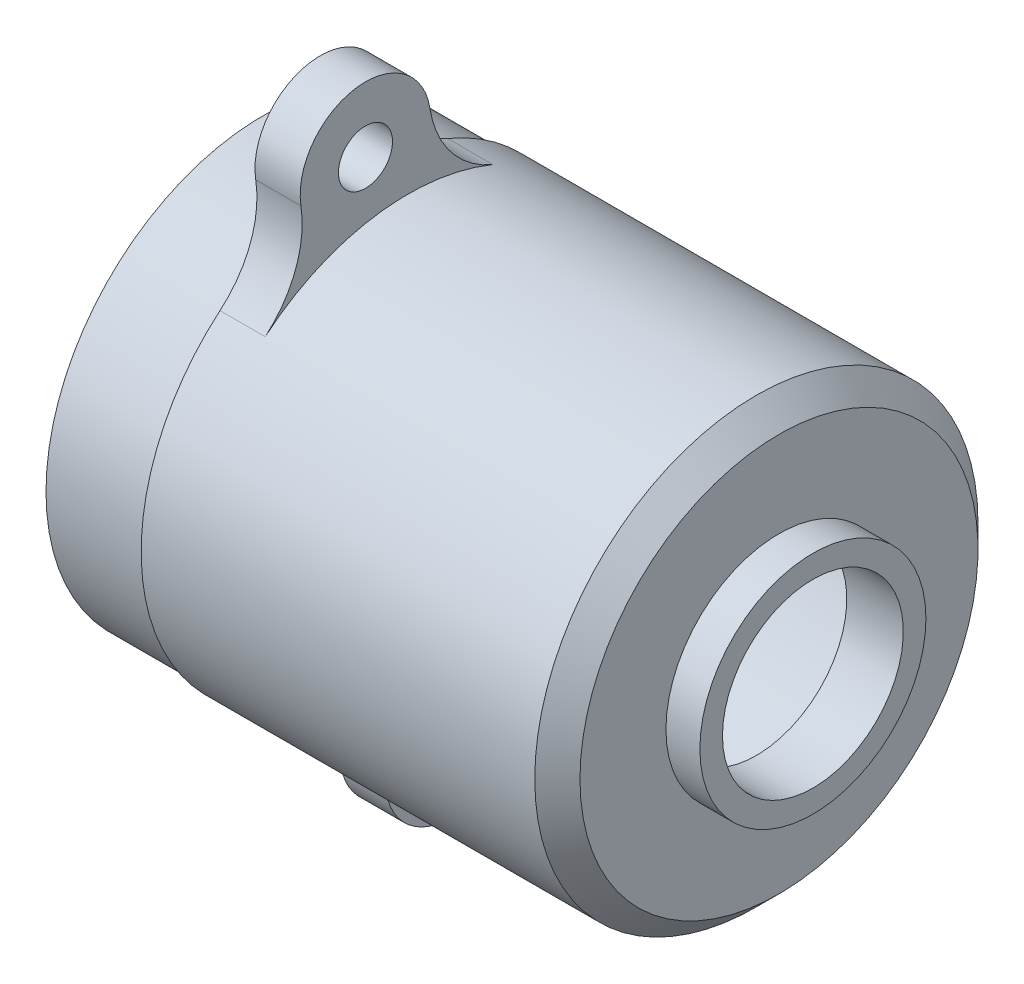
SolidWorks part; units mm, degrees
material "6061-T6 (SS)"
ref_plane "Front Plane" through (0, 0, 0) normal (0, 0, 1) x (1, 0, 0)
ref_plane "Top Plane" through (0, 0, 0) normal (0, 1, 0) x (1, 0, 0)
ref_plane "Right Plane" through (0, 0, 0) normal (1, 0, 0) x (0, 0, -1)
other "Center of Mass"
sketch "Sketch1" plane through (-25.4, 0, 0) normal (1, 0, 0) x (0, 0, -1)
  line L0 (0, 0) -> (-2.9885, 19.3009) construction
  line L1 (-0.1168, 15.7295) -> (1.5403, 20.0021) construction
  line L2 (1.5403, 20.0021) -> (-1.3314, 23.5735) construction
  line L3 (-1.3314, 23.5735) -> (-5.8601, 22.8723) construction
  line L4 (-5.8601, 22.8723) -> (-7.5172, 18.5996) construction
  line L5 (-7.5172, 18.5996) -> (-4.6456, 15.0282) construction
  line L6 (-4.6456, 15.0282) -> (-0.1168, 15.7295) construction
  line L7 (4.6456, -15.0282) -> (0.1168, -15.7295) construction
  line L8 (0.1168, -15.7295) -> (-1.5403, -20.0021) construction
  line L9 (-1.5403, -20.0021) -> (1.3314, -23.5735) construction
  line L10 (1.3314, -23.5735) -> (5.8601, -22.8723) construction
  line L11 (5.8601, -22.8723) -> (7.5172, -18.5996) construction
  line L12 (7.5172, -18.5996) -> (4.6456, -15.0282) construction
  line L13 (-7.5172, 18.5996) -> (1.5403, 20.0021) construction
  line L15 (0, 0) -> (12.0771, 1.87) construction
  circle A0 centre (0, 0) radius 13.9746
  circle A1 centre (0, 0) radius 15.5621 construction
  circle A3 centre (2.9885, -19.3009) radius 3.9688 construction
  circle A4 centre (-2.9885, 19.3009) radius 8.7404 construction
  arc A8 (-10.0273, 11.901) -> (-5.9586, -14.3762) centre (0, 0) ccw
  arc A9 (5.9586, 14.3762) -> (10.0273, -11.901) centre (0, 0) cw
  circle A16 centre (-2.9885, 19.3009) radius 2.667 construction
  circle A17 centre (2.9885, -19.3009) radius 2.667 construction
  arc A18 (-9.6776, 36.4316) -> (-11.5083, 22.6659) centre (127.0686, 11.2409) ccw construction
  arc A19 (4.4842, 36.4316) -> (4.6143, 28.807) centre (76.9988, 33.8561) ccw construction
  arc A20 (-10.0273, 11.901) -> (-7.5172, 18.5996) centre (-14.7303, 17.4828) ccw
  arc A21 (-7.5172, 18.5996) -> (1.5403, 20.0021) centre (-2.9885, 19.3009) cw
  arc A22 (1.5403, 20.0021) -> (5.9586, 14.3762) centre (8.7533, 21.1189) ccw
  arc A23 (7.5172, -18.5996) -> (10.0273, -11.901) centre (14.7303, -17.4828) cw
  arc A24 (-1.5403, -20.0021) -> (7.5172, -18.5996) centre (2.9885, -19.3009) ccw
  arc A25 (-5.9586, -14.3762) -> (-1.5403, -20.0021) centre (-8.7533, -21.1189) cw
  point P4 (-2.3812, 15.3788)
  dimension "D1" = 27.9492
  dimension "D4" = 5.334
  dimension "D2" = 1.5875
  dimension "D3" = 7.9375
extrude "Boss-Extrude1" add sketch "Sketch1" along normal blind 3.175
sketch "Sketch2" plane through (-22.225, 0, 0) normal (1, 0, 0) x (0, 0, -1)
  circle A0 centre (0, 0) radius 13.9746
  circle A1 centre (0, 0) radius 15.5621
  arc A2 (-10.0273, 11.901) -> (-5.9586, -14.3762) centre (0, 0) ccw construction
  circle A3 centre (0, 0) radius 13.9746 construction
extrude "Boss-Extrude2" add sketch "Sketch2" along normal up to surface (24.4625 mm away)
sketch "Sketch5" plane through (0, 0, 0) normal (0, 0, 1) x (1, 0, 0)
  line L1 (6.2063, 7.9375) -> (6.2063, 6.35)
  line L3 (2.2375, -15.5621) -> (2.2375, 15.5621) construction
  line L4 (2.2375, 6.35) -> (2.2375, 15.5621)
  line L5 (0, 0) -> (45.5597, 0) construction
  line L6 (2.2375, 6.35) -> (6.2063, 6.35)
  line L9 (6.2063, 7.9375) -> (3.825, 7.9375)
  line L10 (3.825, 7.9375) -> (3.825, 13.9746)
  line L11 (3.825, 13.9746) -> (2.2375, 15.5621)
  dimension "D2" = 3.9688
  dimension "D1" = 12.7
  dimension "D3" = 1.5875
  dimension "D4" = 1.5875
  dimension "D5" = 45
revolve "Revolve1" add sketch "Sketch5" angle 360 about L5
sketch "Sketch3" plane through (-25.4, 0, 0) normal (-1, 0, 0) x (0, 0, 1)
  circle A0 centre (0, 0) radius 13.9746
  circle A1 centre (0, 0) radius 15.2446
  circle A2 centre (0, 0) radius 13.9746 construction
  dimension "D1" = 1.27
extrude "Boss-Extrude3" add sketch "Sketch3" along normal blind 7
sketch "Sketch6" plane through (0, 0, 0) normal (0, 0, 1) x (1, 0, 0)
  line L0 (-25.4, -23.8836) -> (-25.2163, -23.8836)
  line L1 (-25.4, -23.8836) -> (-22.225, -23.8836) construction
  line L2 (-25.4, -23.8836) -> (-25.4, -25.4)
  line L3 (-25.4, -18.5996) -> (-25.4, -23.8836) construction
  arc A0 (-25.4, -25.4) -> (-25.0498, -27.4796) centre (-19.05, -25.4) ccw construction
  arc A1 (-25.2163, -23.8836) -> (-25.4, -25.4) centre (-19.05, -25.4) cw
extrude "Cut-Extrude1" [suppressed] cut sketch "Sketch6" against normal through all both and the other way through all
hole_wizard "#6 Clearance Hole1" positions "Sketch7" profile "Sketch8" hole size "#6" standard "ANSI Inch" end condition up to next
sketch "Sketch7" plane through (-22.225, 0, 0) normal (1, 0, 0) x (0, 0, -1)
  point P0 (-2.9885, 19.3009)
  point P3 (2.9885, -19.3009)
sketch "Sketch8" plane through (-22.225, 19.3009, 2.9885) normal (0, 1, 0) x (0, 0, -1)
  line L0 (0, 0) -> (0, 3.175)
  line L1 (0, 3.175) -> (1.8986, 3.175)
  line L2 (1.8986, 3.175) -> (1.8986, 0)
  line L5 (1.8986, 0) -> (0, 0)
  line L11 (0, -6.35) -> (0, 107.95) construction
  dimension "Thru Hole Dia." = 3.7973
  dimension "Thru Hole Depth" = 3.175
equation "\"motor diameter\"= 28mm"
equation "\"D1@Sketch1\"=\"motor diameter\"-0.002in"
equation "\"D1@Boss-Extrude3\"=7mm"
equation "\"D2@Sketch5\"=5/32"
